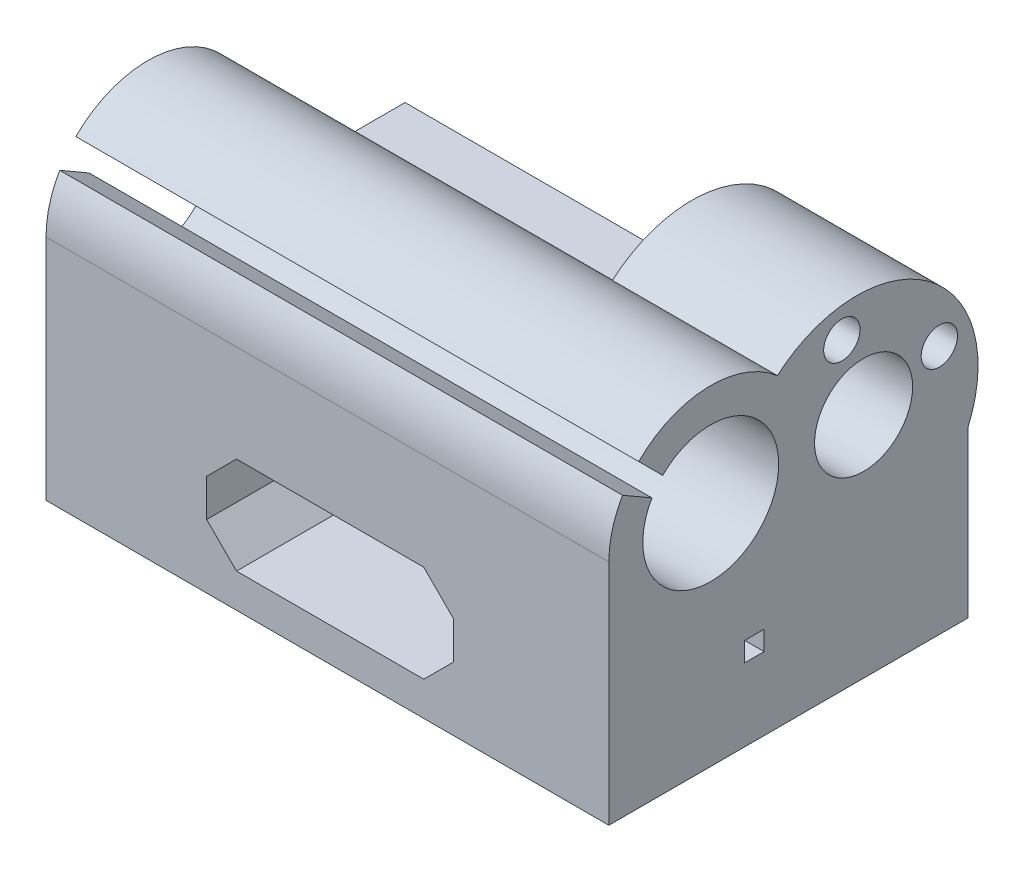
SolidWorks part; units mm, degrees
ref_plane "Front Plane" through (0, 0, 0) normal (0, 0, 1) x (1, 0, 0)
ref_plane "Top Plane" through (0, 0, 0) normal (0, 1, 0) x (1, 0, 0)
ref_plane "Right Plane" through (0, 0, 0) normal (1, 0, 0) x (0, 0, -1)
sketch "Sketch2" plane through (0, 0, 0) normal (0, 1, 0) x (1, 0, 0)
  line L1 (-29, -18.5) -> (29, -18.5)
  line L2 (-29, -18.5) -> (-29, 18.5)
  line L3 (-29, 18.5) -> (29, 18.5)
  line L4 (29, -18.5) -> (29, 18.5)
  line L5 (-29, -18.5) -> (29, 18.5) construction
  line L6 (-29, 18.5) -> (29, -18.5) construction
  point P0 (0, 0)
  dimension "D1" = 58
  dimension "D2" = 37
extrude "Boss-Extrude1" add sketch "Sketch2" along normal blind 17
sketch "Sketch3" plane through (29, 0, 0) normal (1, 0, 0) x (0, 0, -1)
  line L0 (-18.5, 0) -> (18.5, 0) construction
  line L1 (-18.5, 23.5) -> (-18.5, 17)
  line L2 (-18.5, 17) -> (-18.5, 0) construction
  line L5 (2.5, 23.5) -> (2.5, 17)
  line L6 (-18.5, 17) -> (18.5, 17) construction
  line L7 (-18.5, 17) -> (2.5, 17)
  arc A0 (2.5, 23.5) -> (-18.5, 23.5) centre (-8, 23.5) ccw
  dimension "D2" = 21
  dimension "D4" = 23.5
  dimension "D5" = 10.5
extrude "Boss-Extrude2" add sketch "Sketch3" against normal up to surface (58 mm away) up to face at (-29, 8.5, 0)
sketch "Sketch4" plane through (29, 0, 0) normal (1, 0, 0) x (0, 0, -1)
  line L1 (-18.5, 0) -> (18.5, 0) construction
  circle A0 centre (7.0436, 22) radius 12.5
  dimension "D1" = 25
  dimension "D2" = 22
extrude "Boss-Extrude3" add sketch "Sketch4" against normal blind 17
sketch "Sketch5" plane through (0, 0, -18.5) normal (0, 0, -1) x (-1, 0, 0)
  line L0 (-13, 6.57) -> (-13, 10.427)
  line L1 (-13, 10.427) -> (-9.93, 13.497)
  line L2 (-9.93, 13.497) -> (9.37, 13.497)
  line L3 (9.37, 13.497) -> (12.44, 10.427)
  line L4 (12.44, 10.427) -> (12.44, 6.57)
  line L5 (12.44, 6.57) -> (9.37, 3.5)
  line L6 (9.37, 3.5) -> (-9.93, 3.5)
  line L7 (-9.93, 3.5) -> (-13, 6.57)
  line L8 (-29, 0) -> (29, 0) construction
  line L9 (-29, 17) -> (-29, 0) construction
  dimension "D1" = 3.857
  dimension "D2" = 3.857
  dimension "D3" = 135
  dimension "D4" = 135
  dimension "D5" = 3.07
  dimension "D6" = 3.07
  dimension "D7" = 3.07
  dimension "D8" = 3.07
  dimension "D9" = 19.3
  dimension "D10" = 3.5
  dimension "D11" = 16
extrude "Cut-Extrude1" cut sketch "Sketch5" against normal through all
sketch "Sketch6" plane through (0, 0, -18.5) normal (0, 0, -1) x (-1, 0, 0)
  line L0 (-29, 0) -> (29, 0) construction
  line L1 (-29, 17) -> (-29, 0) construction
  circle A0 centre (-23, 8.5) radius 4.076
  circle A1 centre (22, 8.5) radius 4.076
  dimension "D5" = 8.152
  dimension "D6" = 8.152
  dimension "D1" = 8.5
  dimension "D2" = 8.5
  dimension "D3" = 6
  dimension "D4" = 51
extrude "Cut-Extrude2" cut sketch "Sketch6" against normal blind 23
sketch "Sketch7" plane through (29, 0, 0) normal (1, 0, 0) x (0, 0, -1)
  line L0 (-18.5, 23.5) -> (-18.5, 0) construction
  line L1 (-18.5, 0) -> (18.5, 0) construction
  circle A0 centre (-8, 23.5) radius 7
  circle A1 centre (7.7501, 23.5) radius 5.05
  dimension "D1" = 10.1
  dimension "D2" = 14
  dimension "D3" = 26.2501
  dimension "D4" = 23.5
extrude "Cut-Extrude3" cut sketch "Sketch7" against normal through all
sketch "Sketch8" plane through (29, 0, 0) normal (1, 0, 0) x (0, 0, -1)
  line L0 (7.7501, 23.5) -> (5.5097, 31.31) construction
  line L3 (7.7501, 23.5) -> (15.5601, 25.7405) construction
  line L4 (5.5097, 31.31) -> (6.0267, 29.5077) construction
  line L7 (15.5601, 25.7405) -> (13.7578, 25.2235) construction
  circle A1 centre (5.5097, 31.31) radius 1.875
  circle A2 centre (15.5601, 25.7405) radius 1.875
  point P0 (0, 0)
  dimension "D1" = 3.75
  dimension "D2" = 6.25
  dimension "D3" = 3.75
  dimension "D7" = 6.25
extrude "Cut-Extrude4" cut sketch "Sketch8" against normal through all
sketch "Sketch9" plane through (12, 0, 0) normal (-1, 0, 0) x (0, 0, 1)
  circle A0 centre (-5.5097, 31.31) radius 2.75
  circle A1 centre (-15.5601, 25.7405) radius 2.75
  dimension "D1" = 5.5
  dimension "D2" = 5.5
sketch "Sketch10" plane through (29, 0, 0) normal (1, 0, 0) x (0, 0, -1)
  line L0 (-8, 23.5) -> (-15.4246, 30.9246) construction
  line L1 (-8, 23.5) -> (-29.5432, 23.5) construction
  line L2 (-8, 23.5) -> (-17.0933, 28.75) construction
  line L3 (-12.9497, 28.4497) -> (-15.4246, 30.9246)
  line L4 (-17.0933, 28.75) -> (-14.0622, 27)
  arc A0 (-1.1397, 31.449) -> (-18.5, 23.5) centre (-8, 23.5) ccw construction
  arc A1 (-12.9497, 28.4497) -> (-14.0622, 27) centre (-8, 23.5) ccw
  arc A2 (-18.5, 23.5) -> (-17.0933, 28.75) centre (-8, 23.5) ccw
  circle A3 centre (-8, 23.5) radius 7 construction
  circle M9 centre (-8, 23.5) radius 7
  arc M13 (-1.1397, 31.449) -> (-18.5, 23.5) centre (-8, 23.5) ccw
  dimension "D1" = 15
  dimension "D2" = 30
extrude "Cut-Extrude5" cut sketch "Sketch10" against normal through all contours L4 L3 M13 M9 region at (29, 28.8823, 15.0143)
sketch "Sketch12" plane through (-29, 0, 0) normal (-1, 0, 0) x (0, 0, 1)
  line L0 (-18.5, 17) -> (-18.5, 0) construction
  line L1 (4.5, 7.5) -> (2.5, 7.5)
  line L2 (4.5, 7.5) -> (4.5, 9.5)
  line L3 (4.5, 9.5) -> (2.5, 9.5)
  line L4 (2.5, 7.5) -> (2.5, 9.5)
  line L5 (-18.5, 0) -> (18.5, 0) construction
  dimension "D1" = 23
  dimension "D2" = 2
  dimension "D3" = 2
  dimension "D4" = 7.5
extrude "Cut-Extrude6" cut sketch "Sketch12" against normal blind 8
mirror "Mirror1" about plane through (0, 0, 0) normal (1, 0, 0) of "Cut-Extrude6"
